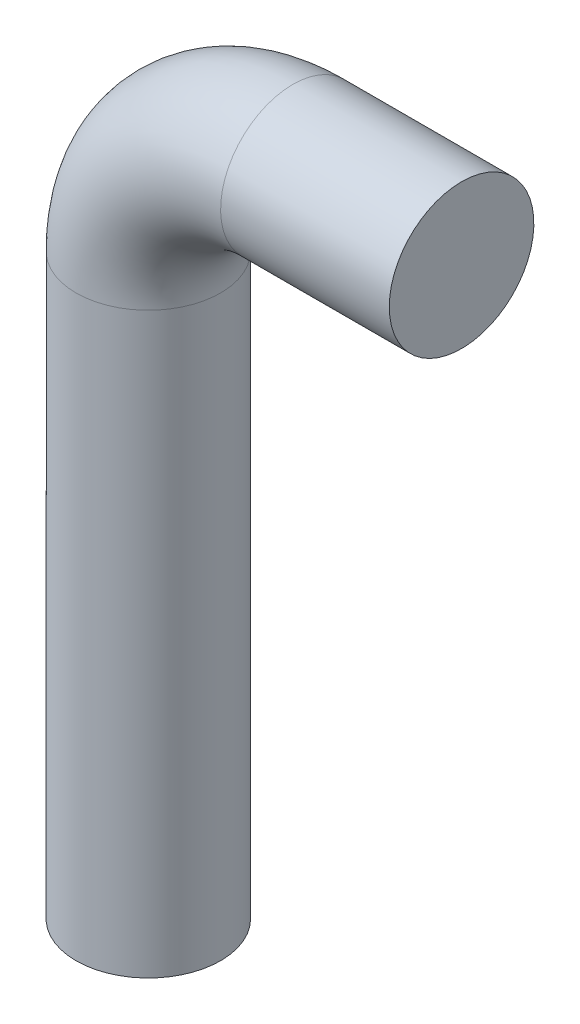
SolidWorks part; units mm, degrees
material "Plain Carbon Steel"
ref_plane "Front Plane" through (0, 0, 0) normal (0, 0, 1) x (1, 0, 0)
ref_plane "Top Plane" through (0, 0, 0) normal (0, 1, 0) x (1, 0, 0)
ref_plane "Right Plane" through (0, 0, 0) normal (1, 0, 0) x (0, 0, -1)
sketch "Sketch1" plane through (0, 0, 0) normal (0, 0, 1) x (1, 0, 0)
  line L0 (0, 0) -> (0, 12)
  line L1 (3, 15) -> (6.5, 15)
  arc A0 (3, 15) -> (0, 12) centre (3, 12) ccw
  dimension "D1" = 12
  dimension "D2" = 3
  dimension "D3" = 12
  dimension "D4" = 3.5
sketch "Sketch2" plane through (0, 0, 0) normal (0, 1, 0) x (1, 0, 0)
  circle A0 centre (0, 0) radius 1.5
  dimension "D1" = 3
sweep "Sweep1" add profiles "Sketch2" path "Sketch1"
ref_axis "Axis1" through (0, 17.325, 0) along (0, -1, 0)
